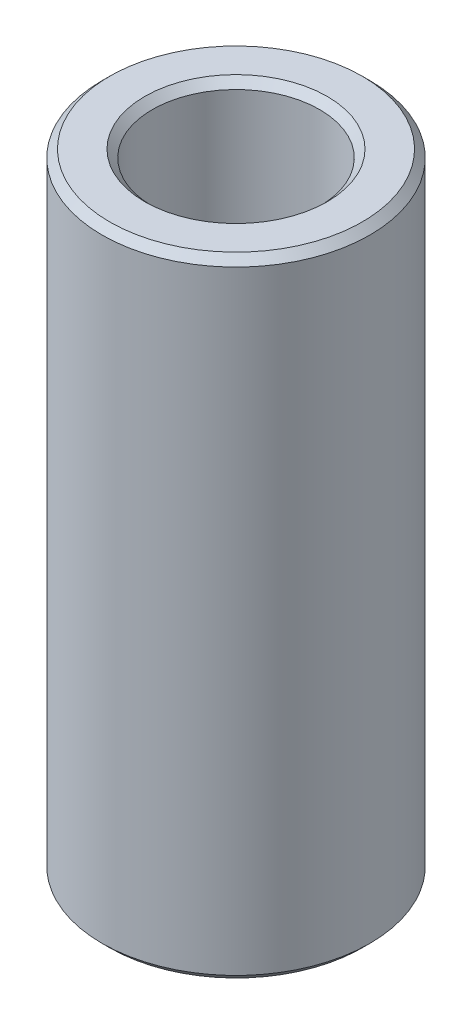
SolidWorks part; units mm, degrees
ref_plane "Front Plane" through (0, 0, 0) normal (0, 0, 1) x (1, 0, 0)
ref_plane "Top Plane" through (0, 0, 0) normal (0, 1, 0) x (1, 0, 0)
ref_plane "Right Plane" through (0, 0, 0) normal (1, 0, 0) x (0, 0, -1)
sketch "Sketch1" plane through (0, 0, 0) normal (0, 1, 0) x (1, 0, 0)
  circle A0 centre (0, 0) radius 37.5
  dimension "SLEEVE_OD" = 75
extrude "Boss-Extrude1" add sketch "Sketch1" along normal blind 176.1187
sketch "Sketch2" plane through (0, 0, 0) normal (0, 1, 0) x (1, 0, 0)
  circle A0 centre (0, 0) radius 23.4401
  dimension "BORE_D" = 46.8801
extrude "Cut-Extrude1" cut sketch "Sketch2" along normal through all
chamfer "Chamfer1" distance 2.1241 angle 45 4 edges at (0, 176.1187, 23.4401) (0, 0, 23.4401) (0, 0, 37.5) (0, 176.1187, 37.5)
